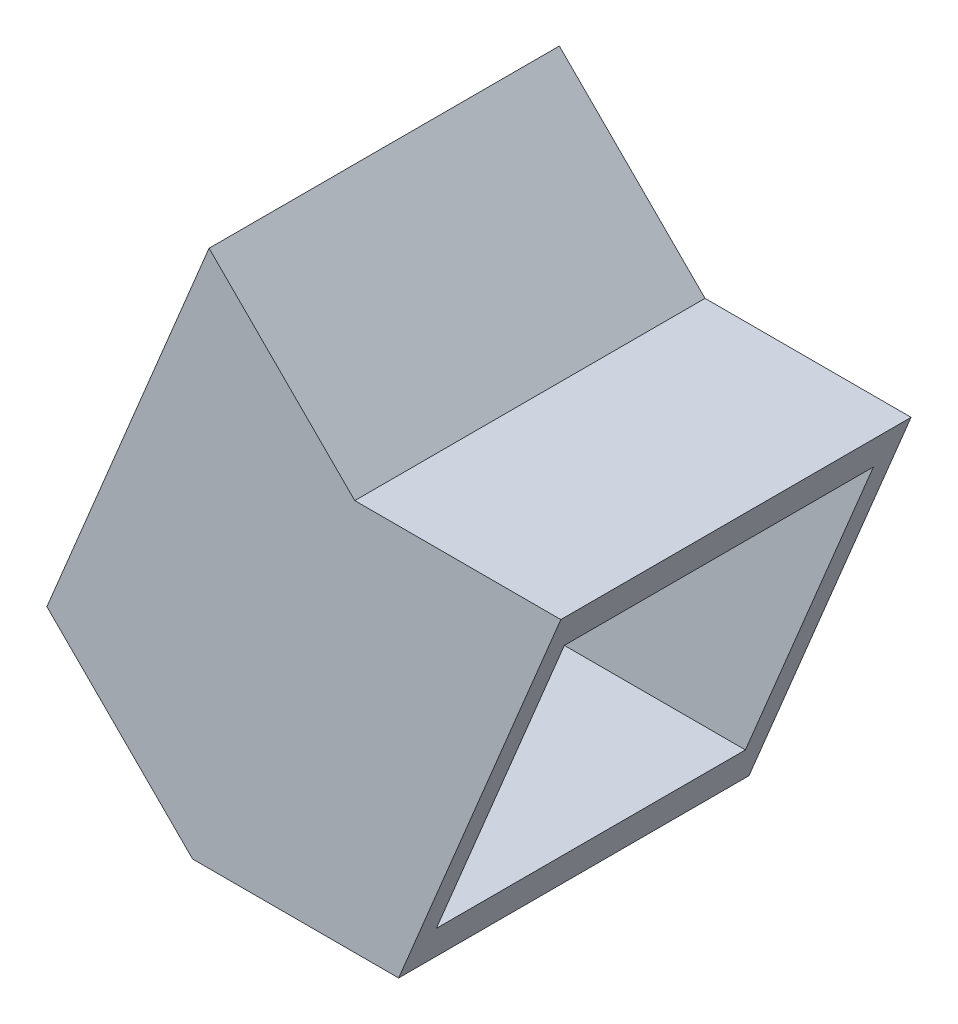
SolidWorks part; units mm, degrees
ref_plane "Plano frontal" through (0, 0, 0) normal (0, 0, 1) x (1, 0, 0)
ref_plane "Plano superior" through (0, 0, 0) normal (0, 1, 0) x (1, 0, 0)
ref_plane "Plano direito" through (0, 0, 0) normal (1, 0, 0) x (0, 0, -1)
sketch "Esboço1" plane through (0, 0, 0) normal (0, 0, 1) x (1, 0, 0)
  line L0 (55.5046, -134) -> (134, -55.5046)
  line L1 (130, 53.8478) -> (53.8478, 130)
  line L2 (53.8478, 130) -> (-53.8478, 130)
  line L3 (-53.8478, 130) -> (-130, 53.8478)
  line L4 (-130, 53.8478) -> (-130, -53.8478)
  line L5 (-130, -53.8478) -> (-53.8478, -130)
  line L6 (-53.8478, -130) -> (53.8478, -130)
  line L7 (53.8478, -130) -> (130, -53.8478)
  line L8 (130, -53.8478) -> (130, 53.8478)
  line L17 (100, 41.4214) -> (41.4214, 100)
  line L18 (41.4214, 100) -> (-41.4214, 100)
  line L19 (-41.4214, 100) -> (-100, 41.4214)
  line L20 (-100, 41.4214) -> (-100, -41.4214)
  line L21 (-100, -41.4214) -> (-41.4214, -100)
  line L22 (-41.4214, -100) -> (41.4214, -100)
  line L23 (41.4214, -100) -> (100, -41.4214)
  line L24 (100, -41.4214) -> (100, 41.4214)
  line L41 (134, 55.5046) -> (55.5046, 134)
  line L42 (55.5046, 134) -> (-55.5046, 134)
  line L43 (-55.5046, 134) -> (-134, 55.5046)
  line L44 (-134, 55.5046) -> (-134, -55.5046)
  line L45 (-134, -55.5046) -> (-55.5046, -134)
  line L46 (-55.5046, -134) -> (55.5046, -134)
  line L47 (134, -55.5046) -> (134, 55.5046)
  line L49 (96, 39.7645) -> (39.7645, 96)
  line L50 (39.7645, 96) -> (-39.7645, 96)
  line L51 (-39.7645, 96) -> (-96, 39.7645)
  line L52 (-96, 39.7645) -> (-96, -39.7645)
  line L53 (-96, -39.7645) -> (-39.7645, -96)
  line L54 (-39.7645, -96) -> (39.7645, -96)
  line L55 (39.7645, -96) -> (96, -39.7645)
  line L56 (96, -39.7645) -> (96, 39.7645)
  circle A0 centre (0, 0) radius 130 construction
  circle A2 centre (0, 0) radius 100 construction
  circle A3 centre (0, 0) radius 134 construction
  circle A4 centre (0, 0) radius 96 construction
extrude "Ressalto-extrusão1" add sketch "Esboço1" along normal blind 34 contours L0 L47 L41 L42 L43 L44 L45 L46 L8 L7 L6 L5 L4 L3 L2 L1 | L23 L24 L17 L18 L19 L20 L21 L22 L56 L55 L54 L53 L52 L51 L50 L49 region at (0, -130.2099, 0) region at (97.1716, 0, 0)
extrude "Ressalto-extrusão2" add sketch "Esboço1<6>" along normal blind 2 contours L7 L8 L1 L2 L3 L4 L5 L6 L24 L23 L22 L21 L20 L19 L18 L17 region at (126.323, 0, 0)
sketch "Esboço1<6>" plane through (0, 0, 0) normal (0, 0, 1) x (1, 0, 0) same geometry as "Esboço1"
extrude "Ressalto-extrusão3" add sketch "Esboço1<7>" against normal blind 2 from surface contours L7 L8 L1 L2 L3 L4 L5 L6 L24 L23 L22 L21 L20 L19 L18 L17 region at (126.323, 0, 0) starting at face at (0, 0, 34)
sketch "Esboço1<7>" plane through (0, 0, 0) normal (0, 0, 1) x (1, 0, 0) same geometry as "Esboço1"
sketch "Esboço2" plane through (0, 0, 34) normal (0, 0, 1) x (1, 0, 0)
  line L0 (-55.5046, -134) -> (-39.7645, -96)
  line L1 (-39.7645, -96) -> (-19.7645, -96)
  line L2 (-39.7645, -96) -> (39.7645, -96) construction
  line L3 (-39.7645, -96) -> (-53.9066, -81.8579)
  line L4 (-96, -39.7645) -> (-39.7645, -96) construction
  line L5 (-55.5046, -134) -> (-69.6468, -119.8579)
  line L6 (-134, -55.5046) -> (-55.5046, -134) construction
  line L7 (-53.9066, -81.8579) -> (-69.6468, -119.8579)
  line L8 (-55.5046, -134) -> (-35.5046, -134)
  line L9 (-55.5046, -134) -> (55.5046, -134) construction
  line L10 (-19.7645, -96) -> (-35.5046, -134)
  line M5 (55.5046, -134) -> (134, -55.5046)
  line M6 (134, -55.5046) -> (134, 55.5046)
  line M7 (134, 55.5046) -> (55.5046, 134)
  line M8 (55.5046, 134) -> (-55.5046, 134)
  line M9 (-55.5046, 134) -> (-134, 55.5046)
  line M10 (-134, 55.5046) -> (-134, -55.5046)
  line M11 (-134, -55.5046) -> (-55.5046, -134)
  line M12 (-55.5046, -134) -> (55.5046, -134)
  line M13 (96, 39.7645) -> (96, -39.7645)
  line M14 (96, -39.7645) -> (39.7645, -96)
  line M15 (39.7645, -96) -> (-39.7645, -96)
  line M16 (-39.7645, -96) -> (-96, -39.7645)
  line M17 (-96, -39.7645) -> (-96, 39.7645)
  line M18 (-96, 39.7645) -> (-39.7645, 96)
  line M19 (-39.7645, 96) -> (39.7645, 96)
  line M20 (39.7645, 96) -> (96, 39.7645)
extrude "Corte-extrusão1" cut sketch "Esboço2" against normal up to next contours L10 L7 M15 M12 M5 M6 M7 M8 M9 M10 M11 M16 M17 M18 M19 M20 M13 M14 region at (-99.1434, -85.0012, 34)
